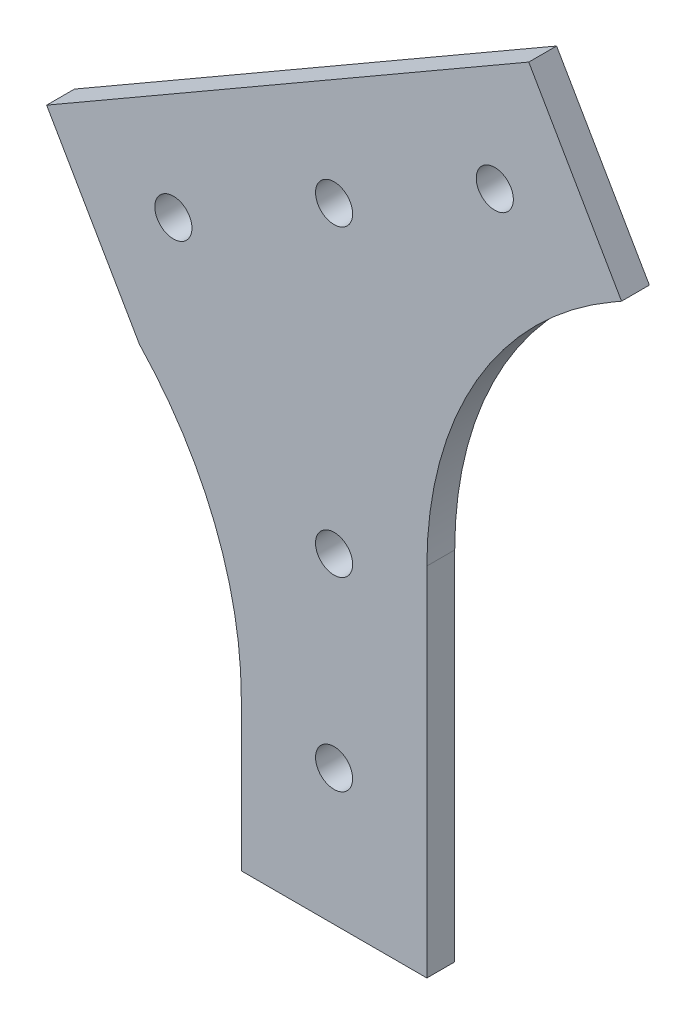
SolidWorks part; units mm, degrees
ref_plane "前视基准面" through (0, 0, 0) normal (0, 0, 1) x (1, 0, 0)
ref_plane "上视基准面" through (0, 0, 0) normal (0, 1, 0) x (1, 0, 0)
ref_plane "右视基准面" through (0, 0, 0) normal (1, 0, 0) x (0, 0, -1)
sketch "草图1" plane through (0, 0, 0) normal (0, 0, 1) x (1, 0, 0)
  line L0 (-30.9808, 35.9808) -> (-20.9808, 18.6603)
  line L1 (-10, 25) -> (10, 25)
  line L2 (-10, 25) -> (-10, -25)
  line L3 (-10, -25) -> (10, -25)
  line L4 (10, 25) -> (10, -25)
  line L5 (-10, 25) -> (10, -25) construction
  line L6 (-10, -25) -> (10, 25) construction
  line L7 (-30.9808, 35.9808) -> (20.9808, 65.9808)
  line L8 (-20.9808, 18.6603) -> (30.9808, 48.6603)
  line L9 (20.9808, 65.9808) -> (30.9808, 48.6603)
  line L10 (-30.9808, 35.9808) -> (30.9808, 48.6603) construction
  line L11 (-20.9808, 18.6603) -> (20.9808, 65.9808) construction
  line L13 (10, 25) -> (10, 36.547)
  line L14 (25.9808, 57.3205) -> (-25.9808, 27.3205) construction
  line L15 (0, -1000) -> (0, 49000) construction
  circle A0 centre (-17.3205, 32.3205) radius 2
  circle A1 centre (17.3205, 52.3205) radius 2
  circle A2 centre (0, 42.3205) radius 2
  point P0 (0, 0)
  point P6 (0, 42.3205)
  dimension "D6" = 4
  dimension "D7" = 4
  dimension "D8" = 20
  dimension "D10" = 4
  dimension "D9" = 20
  dimension "D1" = 50
  dimension "D2" = 20
  dimension "D3" = 60
  dimension "D4" = 20
  dimension "D5" = 60
extrude "凸台-拉伸1" add sketch "草图1" along normal blind 3 contours L1 L13 L8 | L9 L7 L0 L8 A2 A1 A0 | L4 L1 L2 L3 region at (-4.6102, 50.3056, 0) region at (3.3333, 28.849, 0) region at (0, 0, 0)
fillet "圆角1" radius 40 2 edges at (-10, 25, 1.5) (10, 36.547, 1.5)
sketch "草图2" plane through (0, 0, 0) normal (0, 0, -1) x (-1, 0, 0)
  circle A0 centre (0, 9.6018) radius 2 construction
  circle A1 centre (0, -10.3982) radius 2 construction
  circle A2 centre (0, 9.6018) radius 2
  circle A3 centre (0, -10.3982) radius 2
extrude "切除-拉伸1" cut sketch "草图2" against normal blind 10
